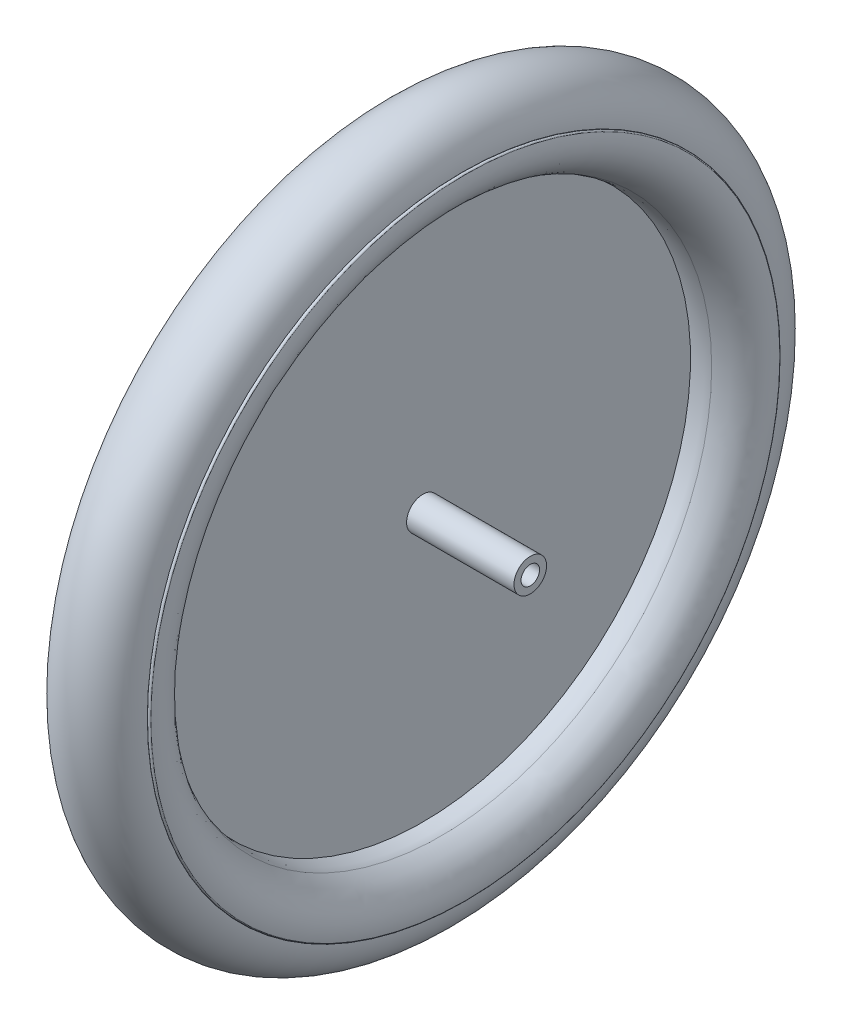
SolidWorks part; units mm, degrees
ref_plane "Front Plane" through (0, 0, 0) normal (0, 0, 1) x (1, 0, 0)
ref_plane "Top Plane" through (0, 0, 0) normal (0, 1, 0) x (1, 0, 0)
ref_plane "Right Plane" through (0, 0, 0) normal (1, 0, 0) x (0, 0, -1)
sketch "Sketch2" plane through (0, 0, 0) normal (0, 0, 1) x (1, 0, 0)
  line L0 (0, 0) -> (0, 145.25) construction
  line L1 (0, 0) -> (50, 0) construction
  line L2 (0, 145.25) -> (0, 170.25) construction
  arc A0 (-22.5, 170.25) -> (22.5, 170.25) centre (0, 170.25) cw
  arc A1 (-22.5, 170.25) -> (-23.9668, 169.7628) centre (-23.0334, 169.4041) ccw
  arc A2 (22.5, 170.25) -> (23.9668, 169.7628) centre (23.0334, 169.4041) cw
  spline S0 degree 3 poles (-23.9668, 169.7628) (-26.7218, 157.7345) (-18.7838, 150.0813) (-10.6716, 146.2584) knots 0 0 0 0 1 1 1 1
  spline S1 degree 3 poles (23.9668, 169.7628) (26.7218, 157.7345) (18.7838, 150.0813) (10.6716, 146.2584) knots 0 0 0 0 1 1 1 1
  spline S2 degree 3 poles (-10.6716, 146.2584) (-5.8194, 143.9718) (6.4023, 143.8524) (10.6716, 146.2584) knots 0 0 0 0 1 1 1 1
  point P11 (0, 144.5)
  dimension "D4" = 22.5
  dimension "D5" = 1
  dimension "D1" = 145.25
  dimension "D2" = 50
  dimension "D3" = 25
  dimension "D6" = 0.75
revolve "Revolve1" add sketch "Sketch2" angle 360 about L1
sketch "Sketch3" plane through (0, 0, 0) normal (1, 0, 0) x (0, 0, -1)
  circle A0 centre (0, 0) radius 5
  circle A1 centre (0, 0) radius 8.8
  dimension "D1" = 10
  dimension "D2" = 17.6
extrude "Boss-Extrude1" add sketch "Sketch3" along normal blind 59 and the other way blind 59 separate body
sketch "Sketch4" plane through (0, 0, 0) normal (1, 0, 0) x (0, 0, -1)
  circle A0 centre (0, 0) radius 146.2584
  dimension "D1" = 292.5168
extrude "Boss-Extrude2" add sketch "Sketch4" along normal blind 1 and the other way blind 1
